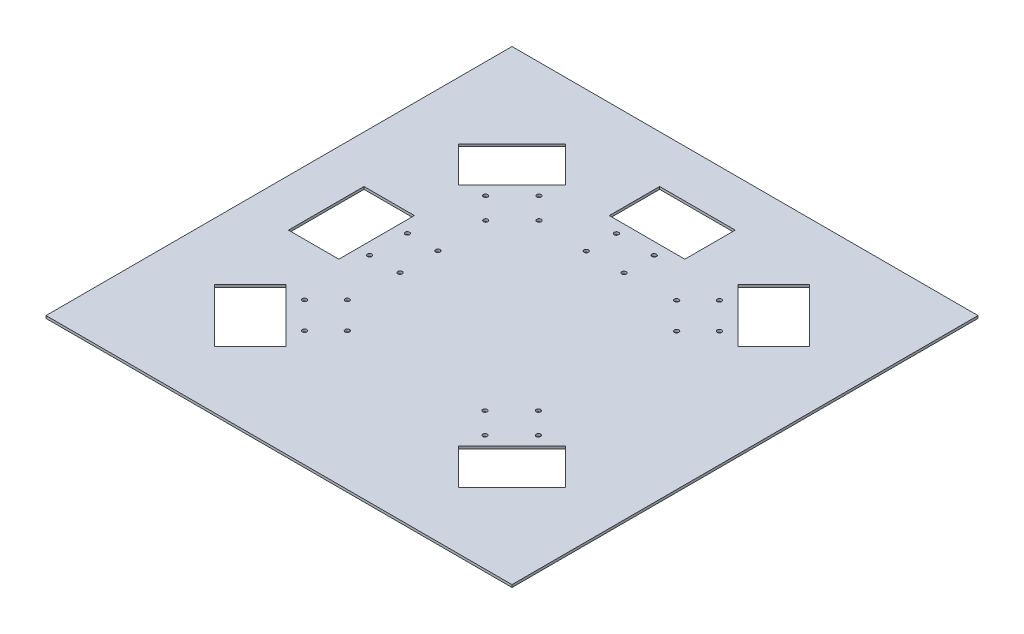
SolidWorks part; units mm, degrees
ref_plane "Front Plane" through (0, 0, 0) normal (0, 0, 1) x (1, 0, 0)
ref_plane "Top Plane" through (0, 0, 0) normal (0, 1, 0) x (1, 0, 0)
ref_plane "Right Plane" through (0, 0, 0) normal (1, 0, 0) x (0, 0, -1)
sketch "Sketch1" plane through (0, 0, 0) normal (0, 1, 0) x (1, 0, 0)
  line L1 (-70.7304, 107.3765) -> (70.7304, 107.3765)
  line L2 (-107.5, 70.607) -> (-107.5, -70.607)
  line L3 (-70.6996, -107.4074) -> (70.7613, -107.4074)
  line L4 (107.5, 70.607) -> (107.5, -70.8539)
  line L5 (-89.7907, 89.7907) -> (89.1307, -89.1307) construction
  line L6 (-89.0535, -89.0535) -> (89.0535, 89.0535) construction
  line L7 (107.5, 70.607) -> (70.7304, 107.3765)
  line L8 (70.7613, -107.4074) -> (107.5, -70.8539)
  line L9 (-107.5, -70.607) -> (-70.6996, -107.4074)
  line L14 (-70.7304, 107.3765) -> (-107.5, 70.607)
  line L15 (-103.2574, 74.8496) -> (-74.9731, 103.1339)
  line L16 (-185, 185) -> (185, -185) construction
  line L17 (-185, 185) -> (185, 185)
  line L18 (-185, 185) -> (-185, -185)
  line L19 (-185, -185) -> (185, -185)
  line L20 (185, 185) -> (185, -185)
  line L21 (185, 185) -> (-185, -185) construction
  line L22 (-89.7907, 89.7907) -> (-103.2574, 103.2574) construction
  line L23 (-89.1152, 88.9917) -> (-118.075, 118.075) construction
  line L24 (-118.075, 118.075) -> (-139.2835, 96.8665) construction
  line L25 (-139.2835, 96.8665) -> (-96.8597, 139.2903) construction
  line L26 (-139.2835, 96.8665) -> (-96.8597, 139.2903)
  line L27 (-139.2835, 96.8665) -> (-110.9992, 68.5823)
  line L28 (0, 0) -> (-107.5, 0) construction
  line L29 (-64.5, 19.656) -> (-64.5, -20.344)
  line L30 (-64.5, 19.656) -> (-107.5, 19.656)
  line L31 (-96.8597, 139.2903) -> (-68.5754, 111.006)
  line L32 (-110.9992, 68.5823) -> (-68.5754, 111.006)
  line L33 (96.8665, 139.2835) -> (139.2903, 96.8597)
  line L34 (-64.5, -20.344) -> (-107.5, -20.344)
  line L35 (-107.5, 19.656) -> (-107.5, -20.344)
  line L36 (-64.5, 19.656) -> (-107.5, -20.344) construction
  line L37 (139.2903, 96.8597) -> (111.006, 68.5754)
  line L38 (68.5823, 110.9992) -> (111.006, 68.5754)
  line L39 (96.8665, 139.2835) -> (68.5823, 110.9992)
  line L40 (-64.5, -20.344) -> (-107.5, 19.656) construction
  line L41 (-107.5, -20.344) -> (-107.5, -15.064) construction
  line L42 (-107.5, -15.064) -> (-97.9995, -15.064) construction
  line L47 (-107.5, 70.607) -> (-107.5, 0) construction
  line L52 (19.7795, 64.3765) -> (19.7795, 107.3765)
  line L53 (19.7795, 64.3765) -> (-20.2205, 64.3765)
  line L59 (-103.2574, 74.8496) -> (-72.8518, 44.444)
  line L61 (-72.8518, 44.444) -> (-44.5675, 72.7283)
  line L62 (-99.5238, 78.5831) -> (-92.8063, 71.8656)
  line L63 (44.444, 72.8518) -> (72.7283, 44.5675)
  line L64 (-74.9731, 103.1339) -> (-72.8518, 44.444) construction
  line L65 (-103.2574, 74.8496) -> (-44.5675, 72.7283) construction
  line L66 (-74.9731, 103.1339) -> (-44.5675, 72.7283)
  line L67 (103.1339, 74.9731) -> (72.7283, 44.5675)
  line L68 (74.8496, 103.2574) -> (44.444, 72.8518)
  line L69 (72.8518, -44.444) -> (44.5675, -72.7283)
  line L70 (74.9731, -103.1339) -> (44.5675, -72.7283)
  line L71 (103.2574, -74.8496) -> (72.8518, -44.444)
  line L72 (-44.444, -72.8518) -> (-72.7283, -44.5675)
  line L73 (-103.1339, -74.9731) -> (-72.7283, -44.5675)
  line L74 (-74.8496, -103.2574) -> (-44.444, -72.8518)
  line L75 (-20.2205, 64.3765) -> (-20.2205, 107.3765)
  line L76 (0, -0.1235) -> (-64.5, 19.656) construction
  line L77 (-107.5, 0) -> (-185, 0) construction
  line L82 (-107.5, 0) -> (-158.075, 0) construction
  line L83 (-107.5, 0) -> (-138.075, 0) construction
  line L88 (-107.5, 0) -> (-127.5, 0) construction
  line L89 (-65.0737, 107.3765) -> (-0.1337, 107.3765) construction
  line L93 (-147.5, 30) -> (-107.5, 30)
  line L95 (-65.0737, 107.3765) -> (-47.5362, 107.3765) construction
  line L96 (-147.5, 30) -> (-147.5, -30)
  line L97 (-147.5, -30) -> (-107.5, -30)
  line L98 (-107.5, 30) -> (-107.5, -30)
  line L99 (-147.5, 30) -> (-107.5, -30) construction
  line L100 (-147.5, -30) -> (-107.5, 30) construction
  line L101 (-0.1337, 107.3765) -> (-0.1337, 185) construction
  line L102 (-0.1337, 107.3765) -> (-0.1337, 127.3765) construction
  line L103 (-107.5, 70.607) -> (-110.3285, 67.7785) construction
  line L104 (-30.1337, 147.3765) -> (29.8663, 147.3765)
  line L105 (-30.1337, 147.3765) -> (-30.1337, 107.3765)
  line L106 (-30.1337, 107.3765) -> (29.8663, 107.3765)
  line L107 (29.8663, 147.3765) -> (29.8663, 107.3765)
  line L108 (-30.1337, 147.3765) -> (29.8663, 107.3765) construction
  line L109 (-30.1337, 107.3765) -> (29.8663, 147.3765) construction
  line L110 (-70.7304, 107.3765) -> (-67.9021, 110.2049) construction
  line L111 (-67.9021, 110.2049) -> (-110.3285, 67.7785)
  line L112 (139.2835, -96.8665) -> (96.8597, -139.2903)
  line L113 (96.8597, -139.2903) -> (68.5754, -111.006)
  line L114 (110.9992, -68.5823) -> (68.5754, -111.006)
  line L115 (139.2835, -96.8665) -> (110.9992, -68.5823)
  line L116 (-96.8665, -139.2835) -> (-139.2903, -96.8597)
  line L117 (-139.2903, -96.8597) -> (-111.006, -68.5754)
  line L118 (-68.5823, -110.9992) -> (-111.006, -68.5754)
  line L119 (-96.8665, -139.2835) -> (-68.5823, -110.9992)
  circle A25 centre (-92.8063, 71.8656) radius 1.75
  circle A26 centre (-75.8358, 54.895) radius 1.75
  circle A27 centre (-71.5931, 93.0788) radius 1.75
  circle A28 centre (-54.6226, 76.1082) radius 1.75
  circle A29 centre (76.1082, 54.6226) radius 1.75
  circle A30 centre (93.0788, 71.5931) radius 1.75
  circle A31 centre (54.895, 75.8358) radius 1.75
  circle A32 centre (71.8656, 92.8063) radius 1.75
  circle A33 centre (54.6226, -76.1082) radius 1.75
  circle A34 centre (71.5931, -93.0788) radius 1.75
  circle A35 centre (75.8358, -54.895) radius 1.75
  circle A36 centre (92.8063, -71.8656) radius 1.75
  circle A37 centre (-76.1082, -54.6226) radius 1.75
  circle A38 centre (-93.0788, -71.5931) radius 1.75
  circle A39 centre (-54.895, -75.8358) radius 1.75
  circle A40 centre (-71.8656, -92.8063) radius 1.75
  circle A41 centre (-97.9995, -15.064) radius 1.75
  circle A42 centre (-97.9995, 14.936) radius 1.75
  circle A43 centre (-73.9309, 15.0595) radius 1.75
  circle A44 centre (-73.9309, -14.9405) radius 1.75
  circle A45 centre (15.0595, 97.876) radius 1.75
  circle A46 centre (15.183, 73.8074) radius 1.75
  circle A47 centre (-14.9405, 97.876) radius 1.75
  circle A48 centre (-14.817, 73.8074) radius 1.75
  point P0 (0, 0)
  point P9 (-89.1152, 89.1152)
  point P18 (0, 0)
  point P19 (-89.1152, 88.9917)
  point P30 (0, 0)
  point P34 (0, 0)
  point P39 (-117.2477, 117.2477)
  point P42 (-118.075, 0.0028)
  point P46 (-86, -0.344)
  point P98 (-0.1496, 0.0261)
  point P148 (0, 0)
  dimension "D5" = 40
  dimension "D6" = 9.5
  dimension "D10" = 4
  dimension "D11" = 3.5
  dimension "D12" = 24
  dimension "D9" = 17.5375
  dimension "D17" = 3.5
  dimension "D19" = 30
  dimension "D20" = 3.5
  dimension "D25" = 30
  dimension "D26" = 2
  dimension "D1" = 141.4609
  dimension "D2" = 215
  dimension "D3" = 52
  dimension "D7" = 40
  dimension "D8" = 5.28
  dimension "D4" = 40
  dimension "D14" = 370
  dimension "D15" = 370
  dimension "D16" = 43
  dimension "D18" = 30
  dimension "D22" = 43
  dimension "D23" = 20
  dimension "D24" = 5.28
  dimension "D27" = 67.4646
  dimension "D28" = 60
  dimension "D29" = 64.94
  dimension "D30" = 20
  dimension "D31" = 60
  dimension "D21" = 4
extrude "Boss-Extrude2" add sketch "Sketch1" along normal blind 2 contours L9 L74 L72 L73 A40 A39 A38 A37 | L7 L68 L63 L67 A32 A31 A30 A29 | L53 L75 L1 L14 L66 L61 L59 L2 L30 L29 L34 L9 L73 L72 L74 L3 L8 L4 L7 L67 L63 L68 L52 A36 A35 A34 A33 | L75 L53 L52 L1 A48 A47 A46 A45 | A25 L15 L14 L59 L61 L66 A28 A27 A26 | L20 L17 L18 L19 L119 L116 L117 L118 L115 L112 L113 L114 L39 L33 L37 L38 L32 L27 L26 L31 L104 L107 L1 L7 L4 L8 L3 L9 L2 L97 L96 L93 L14 L15 | L34 L29 L30 L2 A44 A43 A42 A41 region at (7.8394, 0, 7.8112) region at (-73.917, 0, -73.7844) region at (-0.2283, 0, -85.8773) region at (73.7844, 0, -73.917) region at (-86.0008, 0, 0.3518) region at (-73.7844, 0, 73.917) region at (0, 0, -179.7674)
